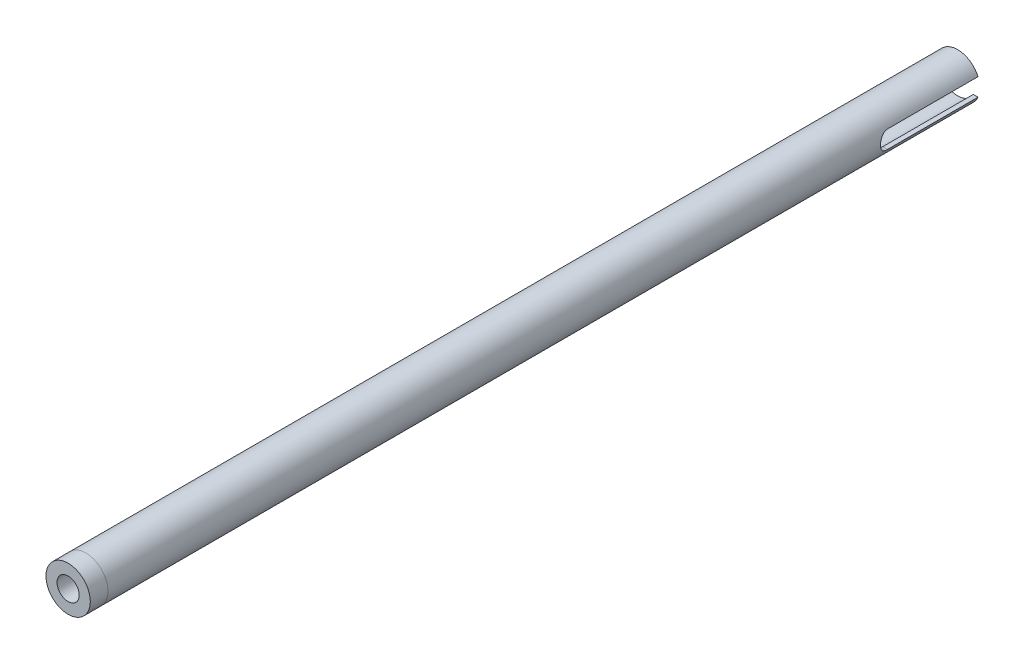
SolidWorks part; units mm, degrees
ref_plane "Front Plane" through (0, 0, 0) normal (0, 0, 1) x (1, 0, 0)
ref_plane "Top Plane" through (0, 0, 0) normal (0, 1, 0) x (1, 0, 0)
ref_plane "Right Plane" through (0, 0, 0) normal (1, 0, 0) x (0, 0, -1)
sketch "Axis" plane through (0, 0, 0) normal (0, 1, 0) x (1, 0, 0)
  line L0 (0, 0) -> (0, 318.4826) construction
  line L1 (0, 0) -> (0, -34.925) construction
  line L2 (0, 318.4826) -> (-7.9375, 318.4826) construction
  line L4 (0, 347.2669) -> (-10.3187, 309.8472) construction
  dimension "D1" = 34.925
  dimension "D2" = 7.9375
sketch "Sketch1" plane through (0, 0, 0) normal (0, 0, 1) x (1, 0, 0)
  line L0 (-7.9375, 0) -> (7.9375, 0) construction
  line L1 (-7.2748, 3.175) -> (7.2748, 3.175)
  line L2 (-7.2748, -3.175) -> (7.2748, -3.175)
  circle A0 centre (0, 0) radius 7.9375
  circle A1 centre (0, 0) radius 6.4135
  circle A2 centre (0, 0) radius 3.9688
  dimension "D1" = 15.875
  dimension "D3" = 7.9375
  dimension "D2" = 1.524
  dimension "D4" = 6.35
extrude "Threaded insert 1-1" add sketch "Sketch1" against normal blind 6.35 contours A2 L1 A1 | A1 L1 A0 | A2 L0 A1 L1 | A1 L0 A0 L1 | L0 A1 L2 A0 | L0 A2 L2 A1 | A2 L2 A1 | A1 L2 A0 | L0 A1 L2 A2 | L0 A0 L2 A1 | A0 L0 A1 L1 | A1 L0 A2 L1 region at (4.7887, 1.6543, 0) region at (4.7887, -1.6543, 0) region at (6.9234, 1.6163, 0) region at (6.9234, -1.6163, 0) region at (-4.7887, -1.6543, 0) region at (-4.7887, 1.6543, 0) region at (0, 4.6159, 0) region at (0, -4.6159, 0) region at (0, 6.5666, 0) region at (6.4237, -3.3281, 0) region at (-6.9234, -1.6163, 0) region at (-6.9234, 1.6163, 0)
extrude "Threaded insert 1-2" add sketch "Sketch1<3>" against normal blind 9.525 from surface contours A2 L1 A1 | A2 L0 A1 L1 | L0 A2 L2 A1 | A2 L2 A1 | L0 A1 L2 A2 | A1 L0 A2 L1 region at (4.7887, 1.6543, 0) region at (4.7887, -1.6543, 0) region at (-4.7887, -1.6543, 0) region at (-4.7887, 1.6543, 0) region at (0, 4.6159, 0) region at (0, -4.6159, 0) starting at face at (7.9375, 0, -6.35)
sketch "Sketch1<3>" plane through (0, 0, 0) normal (0, 0, 1) x (1, 0, 0) same geometry as "Sketch1"
extrude "A-arm tube" add sketch "Sketch1<4>" against normal up to vertex (318.4826 mm away) from surface separate body contours A1 L1 A0 | A1 L0 A0 L1 | L0 A1 L2 A0 | A1 L2 A0 | L0 A0 L2 A1 | A0 L0 A1 L1 region at (6.9234, 1.6163, 0) region at (6.9234, -1.6163, 0) region at (0, 6.5666, 0) region at (6.4237, -3.3281, 0) region at (-6.9234, -1.6163, 0) region at (-6.9234, 1.6163, 0) up to point (0, 0, -318.4826) starting at face at (6.4135, 0, -6.35)
sketch "Sketch1<4>" plane through (0, 0, 0) normal (0, 0, 1) x (1, 0, 0) same geometry as "Sketch1"
extrude "Apex slot" cut sketch "Sketch1<5>" along normal blind 35.56 from surface contours A0 L0 A1 L1 | L0 A0 L2 A1 | A1 L0 A0 L1 | L0 A1 L2 A0 region at (6.9234, 1.6163, 0) region at (6.9234, -1.6163, 0) region at (-6.9234, -1.6163, 0) region at (-6.9234, 1.6163, 0) starting at face at (6.4135, 0, -318.4826)
sketch "Sketch1<5>" plane through (0, 0, 0) normal (0, 0, 1) x (1, 0, 0) same geometry as "Sketch1"
fillet "Fillet1" radius 3.175 4 edges at (-6.4237, 3.175, -282.9226) (-6.4237, -3.175, -282.9226) (6.4237, -3.175, -282.9226) (6.4237, 3.175, -282.9226)
equation "\"tube diameter\"= 5 / 8"
equation "\"tube thickness\"= .06"
equation "\"apex thickness\"= .25"
equation "\"tube slot\"= 1.4"
equation "\"D1@Sketch1\"=\"tube diameter\""
equation "\"D2@Sketch1\"=\"tube thickness\""
equation "\"threaded insert hole\"= .3125"
equation "\"D3@Sketch1\"=\"threaded insert hole\""
equation "\"D4@Sketch1\"=\"apex thickness\""
equation "\"D1@Apex slot\" = \"tube slot\""
equation "\"D1@Fillet1\"=\"apex thickness\"/2"
equation "\"D2@Axis\"=\"tube diameter\"/2"
